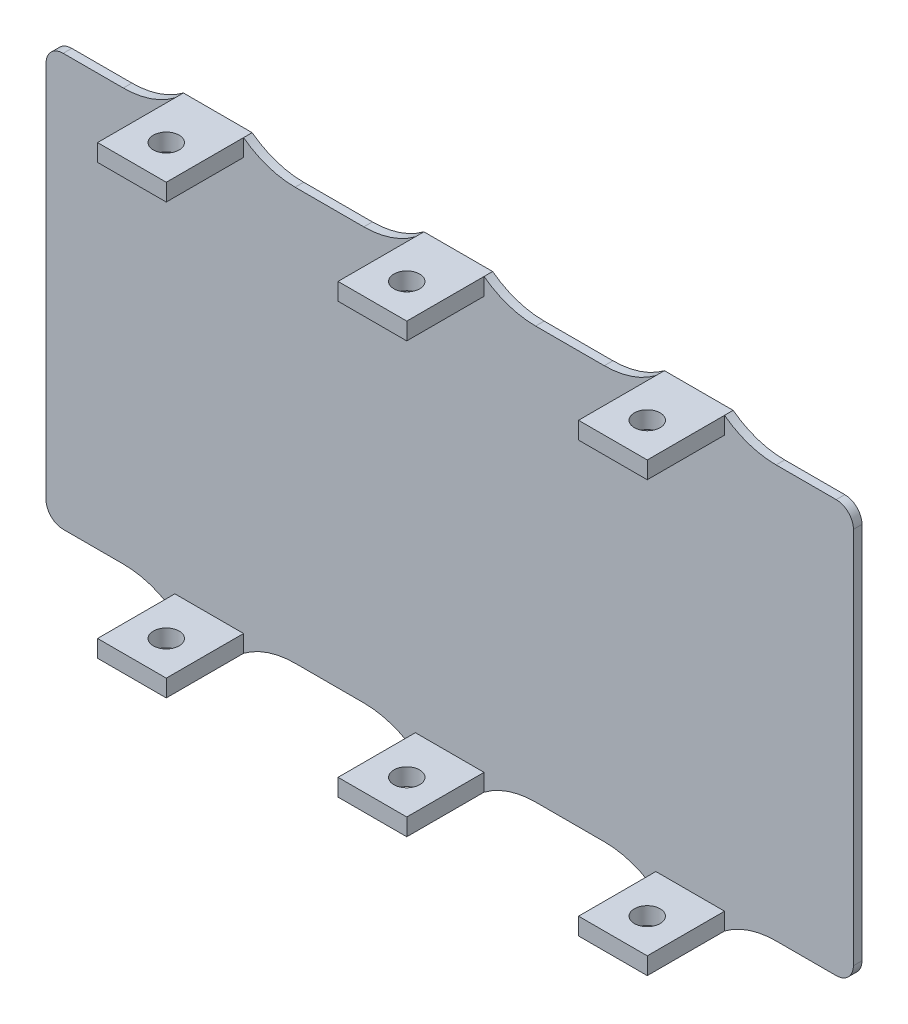
SolidWorks part; units mm, degrees
ref_plane "Front Plane" through (0, 0, 0) normal (0, 0, 1) x (1, 0, 0)
ref_plane "Top Plane" through (0, 0, 0) normal (0, 1, 0) x (1, 0, 0)
ref_plane "Right Plane" through (0, 0, 0) normal (1, 0, 0) x (0, 0, -1)
sketch "Эскиз1" plane through (0, 0, 0) normal (0, 0, 1) x (1, 0, 0)
  line L1 (-47, -24) -> (47, -24)
  line L2 (-47, -24) -> (-47, 24)
  line L3 (-47, 24) -> (47, 24)
  line L4 (47, -24) -> (47, 24)
  line L5 (-47, -24) -> (47, 24) construction
  line L6 (-47, 24) -> (47, -24) construction
  point P0 (0, 0)
  dimension "D1" = 48
  dimension "D2" = 94
extrude "Бобышка-Вытянуть1" add sketch "Эскиз1" along normal blind 1
sketch "Эскиз2" plane through (0, -24, 0) normal (0, -1, 0) x (1, 0, 0)
  line L0 (-47, 0) -> (47, 0) construction
  line L1 (-32, 0) -> (-24, 0)
  line L2 (-32, 0) -> (-32, 10)
  line L3 (-32, 10) -> (-24, 10)
  line L4 (-24, 0) -> (-24, 10)
  line L5 (-47, 1) -> (-47, 0) construction
  line L6 (47, 1) -> (47, 0) construction
  line L7 (24, 0) -> (32, 0)
  line L8 (24, 0) -> (24, 10)
  line L9 (24, 10) -> (32, 10)
  line L10 (32, 0) -> (32, 10)
  line L12 (-4, 0) -> (4, 0)
  line L13 (-4, 0) -> (-4, 10)
  line L14 (-4, 10) -> (4, 10)
  line L15 (4, 0) -> (4, 10)
  dimension "D1" = 15
  dimension "D2" = 8
  dimension "D3" = 8
  dimension "D4" = 15
  dimension "D5" = 8
  dimension "D6" = 10
  dimension "D7" = 10
  dimension "D8" = 10
  dimension "D9" = 20
  dimension "D10" = 20
extrude "Бобышка-Вытянуть2" add sketch "Эскиз2" along normal blind 2
mirror "Зеркальное отражение1" about plane through (0, 0, 0) normal (0, 1, 0) of "Бобышка-Вытянуть2"
fillet "Скругление1" radius 10 12 edges at (-32, 24, 0.5) (-24, 24, 0.5) (-4, 24, 0.5) (4, 24, 0.5) (24, 24, 0.5) (32, 24, 0.5) (32, -24, 0.5) (24, -24, 0.5) (4, -24, 0.5) (-4, -24, 0.5) (-24, -24, 0.5) (-32, -24, 0.5)
sketch "Эскиз3" plane through (0, -26, 0) normal (0, -1, 0) x (1, 0, 0)
  line L0 (-24, 10) -> (-32, 10) construction
  line L1 (-32, 10) -> (-32, 1) construction
  line L2 (4, 10) -> (-4, 10) construction
  line L3 (-4, 10) -> (-4, 1) construction
  line L4 (32, 10) -> (24, 10) construction
  line L5 (24, 10) -> (24, 1) construction
  circle A0 centre (-28, 6) radius 1.5
  circle A1 centre (0, 6) radius 1.5
  circle A2 centre (28, 6) radius 1.5
  dimension "D3" = 3
  dimension "D6" = 3
  dimension "D7" = 3
  dimension "D1" = 4
  dimension "D2" = 4
  dimension "D4" = 4
  dimension "D5" = 4
  dimension "D8" = 4
  dimension "D9" = 4
extrude "Вырез-Вытянуть1" cut sketch "Эскиз3" against normal through all
fillet "Скругление2" radius 2 4 edges at (47, 24, 0.5) (47, -24, 0.5) (-47, -24, 0.5) (-47, 24, 0.5)
